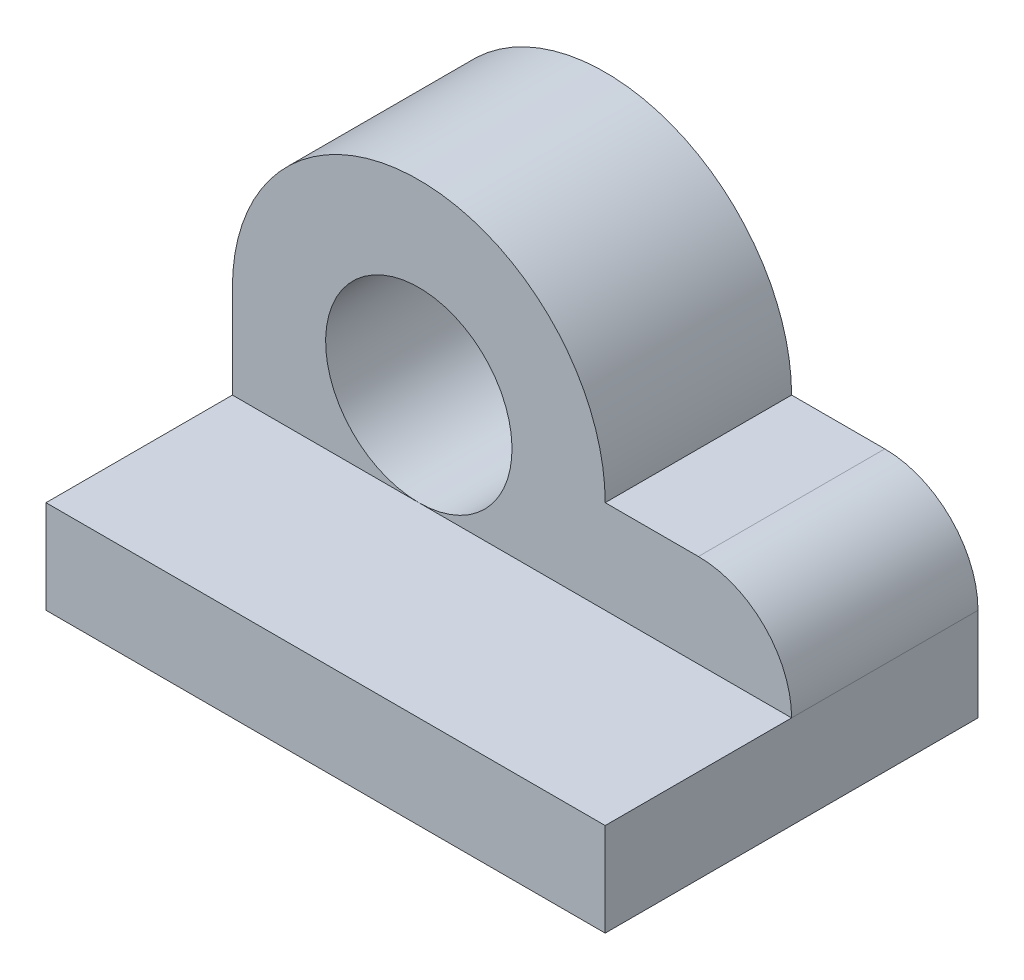
SolidWorks part; units mm, degrees
ref_plane "Front Plane" through (0, 0, 0) normal (0, 0, 1) x (1, 0, 0)
ref_plane "Top Plane" through (0, 0, 0) normal (0, 1, 0) x (1, 0, 0)
ref_plane "Right Plane" through (0, 0, 0) normal (1, 0, 0) x (0, 0, -1)
sketch "Sketch1" plane through (0, 0, 0) normal (0, 0, 1) x (1, 0, 0)
  line L0 (0, 0) -> (0, 56.7857) construction
  line L1 (-20, 18.3928) -> (40, 18.3928)
  line L3 (-20, 8.3928) -> (40, 8.3928)
  line L4 (-20, 28.3928) -> (-20, 8.3928)
  line L5 (40, 8.3928) -> (40, 28.3928)
  line L6 (40, 28.3928) -> (20, 28.3928)
  arc A0 (20, 28.3928) -> (-20, 28.3928) centre (0, 28.3928) ccw
  circle A1 centre (0, 28.3928) radius 10
  dimension "D1" = 60
  dimension "D2" = 20
  dimension "D3" = 20
  dimension "D4" = 20
  dimension "D5" = 10
extrude "Boss-Extrude2" add sketch "Sketch1" along normal blind 40 contours L3 L0 L1 L4 | L0 L3 L5 L1 region at (-10, 13.3928, 0) region at (20, 13.3928, 0)
extrude "Boss-Extrude5" add sketch "Sketch1<6>" along normal blind 20 contours L0 A1 L1 L5 L6 A0 region at (17.9508, 29.5896, 0)
sketch "Sketch1<6>" plane through (0, 0, 0) normal (0, 0, 1) x (1, 0, 0) same geometry as "Sketch1"
extrude "Boss-Extrude6" add sketch "Sketch1<7>" along normal blind 20 contours A1 L0 A0 L4 L1 region at (-11.202, 33.0603, 0)
sketch "Sketch1<7>" plane through (0, 0, 0) normal (0, 0, 1) x (1, 0, 0) same geometry as "Sketch1"
fillet "Fillet1" radius 10 1 edges at (40, 28.3928, 10)
